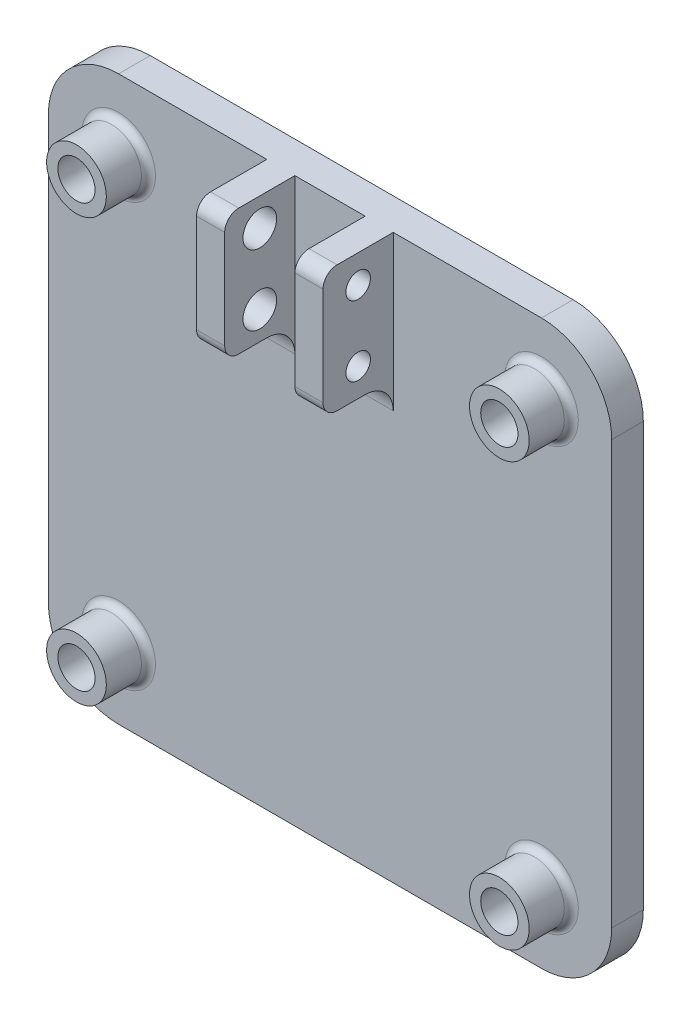
SolidWorks part; units mm, degrees
ref_plane "Front Plane" through (0, 0, 0) normal (0, 0, 1) x (1, 0, 0)
ref_plane "Top Plane" through (0, 0, 0) normal (0, 1, 0) x (1, 0, 0)
ref_plane "Right Plane" through (0, 0, 0) normal (1, 0, 0) x (0, 0, -1)
sketch "Sketch1" plane through (0, 0, 0) normal (0, 0, 1) x (1, 0, 0)
  line L0 (-30.1, 0) -> (30.1, 0) construction
  line L1 (-40.1, -40.1) -> (40.1, -40.1)
  line L2 (-40.1, -40.1) -> (-40.1, 40.1)
  line L3 (-40.1, 40.1) -> (40.1, 40.1)
  line L4 (40.1, -40.1) -> (40.1, 40.1)
  line L5 (-40.1, -40.1) -> (40.1, 40.1) construction
  line L6 (-40.1, 40.1) -> (40.1, -40.1) construction
  line L7 (55, 0) -> (-55, 0) construction
  line L8 (-30.1, -30.1) -> (-30.1, 30.1) construction
  line L9 (30.1, -30.1) -> (30.1, 30.1) construction
  point P0 (0, 0)
  point P11 (0, 0)
  point P14 (-30.1, 0)
  point P17 (30.1, 0)
  dimension "D1" = 60.2
  dimension "D2" = 10
  dimension "D3" = 10
extrude "Boss-Extrude1" add sketch "Sketch1" along normal blind 4.5 contours L2 L3 L4 L1
hole_wizard "M5 Clearance Hole1" positions "3DSketch1" profile "Sketch2" hole size "M5" standard "ANSI Metric" end condition through all
sketch3d "3DSketch1"
  point P0 (30.1, 30.1, 0)
  point P2 (-30.1, 30.1, 0)
  point P4 (-30.1, -30.1, 0)
  point P6 (30.1, -30.1, 0)
sketch "Sketch2" plane through (30.1, 30.1, 0) normal (1, 0, 0) x (0, 1, 0)
  line L0 (0, 0) -> (0, 4.5)
  line L1 (0, 4.5) -> (2.65, 4.5)
  line L2 (2.65, 4.5) -> (2.65, 0)
  line L5 (2.65, 0) -> (0, 0)
  line L11 (0, -6.35) -> (0, 107.95) construction
  dimension "Thru Hole Dia." = 5.3
  dimension "Thru Hole Depth" = 4.5
fillet "Fillet1" radius 10 4 edges at (-40.1, 40.1, 2.25) (-40.1, -40.1, 2.25) (40.1, -40.1, 2.25) (40.1, 40.1, 2.25)
sketch "Sketch3" plane through (0, 0, 4.5) normal (0, 0, 1) x (1, 0, 0)
  line L1 (-9, 40.1) -> (-5, 40.1)
  line L2 (-9, 40.1) -> (-9, 22.1)
  line L3 (-9, 22.1) -> (-5, 22.1)
  line L4 (-5, 40.1) -> (-5, 22.1)
  line L5 (9, 22.1) -> (5, 22.1)
  line L6 (9, 22.1) -> (9, 40.1)
  line L7 (9, 40.1) -> (5, 40.1)
  line L8 (5, 22.1) -> (5, 40.1)
  line L9 (-30.1, 40.1) -> (30.1, 40.1) construction
  line L10 (5, 31.1) -> (-5, 31.1) construction
  line L11 (0, -2.475) -> (0, 2.475) construction
  point P8 (0, 31.1)
  dimension "D1" = 10
  dimension "D2" = 4
  dimension "D3" = 4
  dimension "D4" = 18
extrude "Boss-Extrude2" add sketch "Sketch3" along normal blind 10
sketch "Sketch5" plane through (9, 0, 0) normal (1, 0, 0) x (0, 0, -1)
  line L0 (-9.5, 40.1) -> (-9.5, 22.1) construction
  line L2 (-14.5, 40.1) -> (-4.5, 40.1) construction
  line L3 (-14.5, 22.1) -> (-4.5, 22.1) construction
  circle A0 centre (-9.5, 36.1) radius 1.75
  circle A1 centre (-9.5, 26.1) radius 1.75
  dimension "D1" = 3.5
  dimension "D2" = 10
  dimension "D3" = 4
extrude "Cut-Extrude1" cut sketch "Sketch5" against normal up to next
sketch "Sketch6" plane through (-9, 0, 0) normal (-1, 0, 0) x (0, 0, 1)
  line L0 (9.5, 40.1) -> (9.5, 22.1) construction
  line L1 (14.5, 40.1) -> (4.5, 40.1) construction
  line L2 (14.5, 22.1) -> (4.5, 22.1) construction
  circle A0 centre (9.5, 36.1) radius 2.4
  circle A1 centre (9.5, 26.1) radius 2.4
  dimension "D1" = 4.8
  dimension "D2" = 10
  dimension "D3" = 4
extrude "Cut-Extrude2" cut sketch "Sketch6" against normal up to next
fillet "Fillet2" radius 2 4 edges at (-7, 22.1, 14.5) (7, 22.1, 14.5) (7, 40.1, 14.5) (-7, 40.1, 14.5)
fillet "Fillet3" radius 4 2 edges at (7, 22.1, 4.5) (-7, 22.1, 4.5)
sketch "Sketch7" plane through (0, 0, 4.5) normal (0, 0, 1) x (1, 0, 0)
  circle A0 centre (-30.1, 30.1) radius 4.25
  circle A1 centre (-30.1, -30.1) radius 2.65 construction
  circle A2 centre (30.1, -30.1) radius 2.65 construction
  circle A3 centre (30.1, 30.1) radius 2.65 construction
  circle A4 centre (-30.1, 30.1) radius 2.65 construction
  circle A5 centre (-30.1, -30.1) radius 2.65
  circle A6 centre (30.1, -30.1) radius 2.65
  circle A7 centre (30.1, 30.1) radius 2.65
  circle A8 centre (-30.1, 30.1) radius 2.65
  circle A9 centre (30.1, 30.1) radius 4.25
  circle A10 centre (30.1, -30.1) radius 4.25
  circle A11 centre (-30.1, -30.1) radius 4.25
  dimension "D1" = 8.5
extrude "Boss-Extrude3" add sketch "Sketch7" along normal blind 6
fillet "Fillet5" radius 1 4 edges at (34.35, 30.1, 4.5) (34.35, -30.1, 4.5) (-25.85, -30.1, 4.5) (-25.85, 30.1, 4.5)
